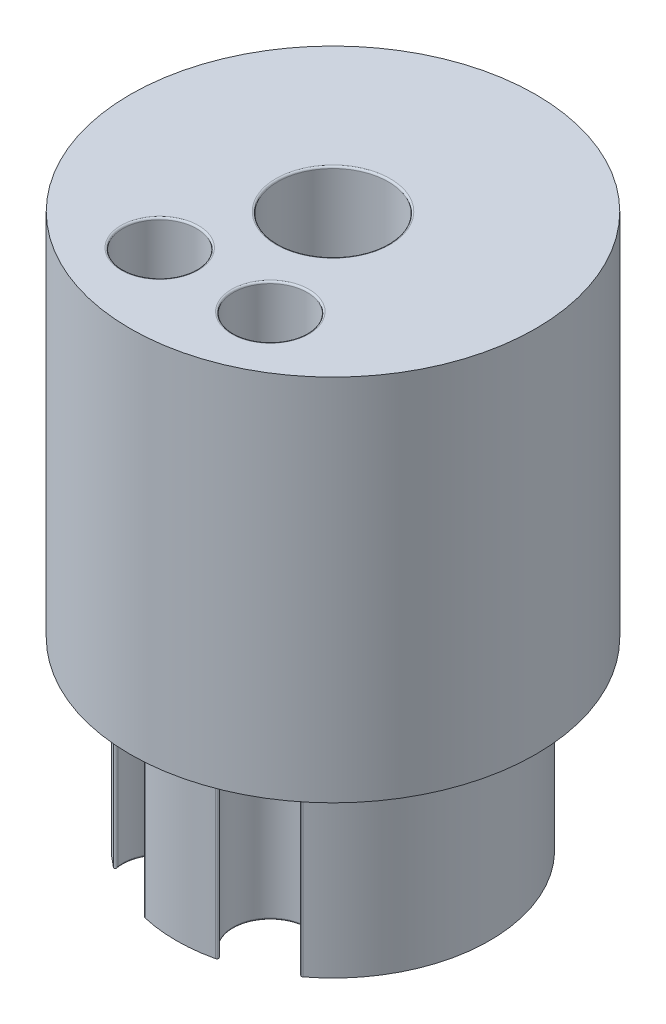
SolidWorks part; units mm, degrees
material "1060 Alloy"
ref_plane "Front Plane" through (0, 0, 0) normal (0, 0, 1) x (1, 0, 0)
ref_plane "Top Plane" through (0, 0, 0) normal (0, 1, 0) x (1, 0, 0)
ref_plane "Right Plane" through (0, 0, 0) normal (1, 0, 0) x (0, 0, -1)
sketch "Sketch1" plane through (0, 0, 0) normal (0, 1, 0) x (1, 0, 0)
  circle A0 centre (0, 0) radius 0.55
  dimension "D1" = 1.1
extrude "Boss-Extrude1" add sketch "Sketch1" against normal blind 1
sketch "Sketch2" plane through (0, -1, 0) normal (0, -1, 0) x (1, 0, 0)
  circle A0 centre (0, 0) radius 0.425
  dimension "D1" = 0.85
extrude "Boss-Extrude2" add sketch "Sketch2" along normal blind 0.5
sketch "Sketch3" plane through (0, 0, 0) normal (0, 1, 0) x (1, 0, 0)
  line L0 (0, 0) -> (0, -0.425) construction
  line L1 (-0.15, -0.32) -> (0.15, -0.32) construction
  circle A0 centre (0, 0) radius 0.15
  circle A1 centre (0, 0) radius 0.425 construction
  circle A2 centre (0, 0) radius 0.425 construction
  circle A3 centre (0.15, -0.32) radius 0.1
  circle A4 centre (-0.15, -0.32) radius 0.1
  dimension "D1" = 0.3
  dimension "D4" = 0.32
  dimension "D5" = 0.2
  dimension "D2" = 0.15
  dimension "D3" = 0.15
extrude "Cut-Extrude1" cut sketch "Sketch3" against normal through all
fillet "Fillet5" radius 0.005 12 edges at (0, 0, 0.15) (0, -1.5, 0.15) (0.15, 0, 0.42) (0.1076, -1.5, 0.2295) (-0.15, 0, 0.42) (-0.1076, -1.5, 0.2295) (0.2465, -1.25, 0.3462) (0.1084, -1.25, 0.4109) (0.1924, -1, 0.4105) (-0.1084, -1.25, 0.4109) (-0.2465, -1.25, 0.3462) (-0.1924, -1, 0.4105)
